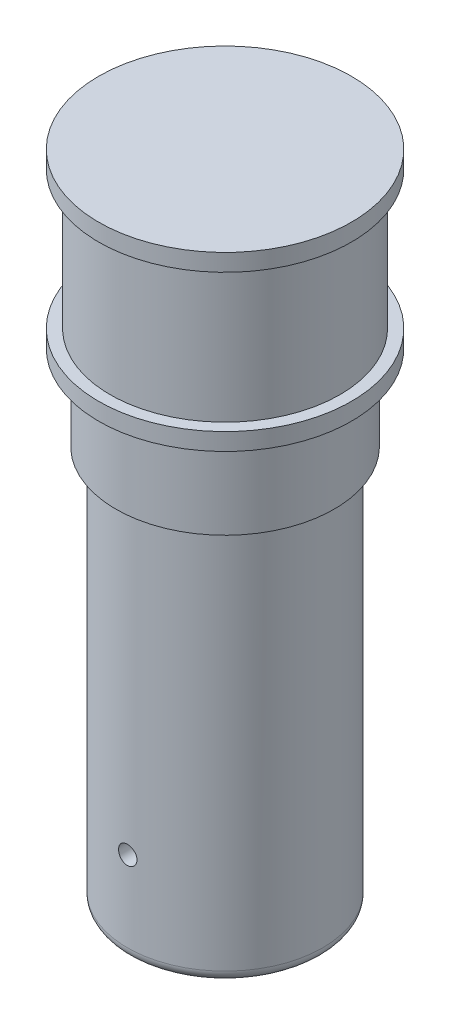
SolidWorks part; units mm, degrees
material "ABS"
ref_plane "Front Plane" through (0, 0, 0) normal (0, 0, 1) x (1, 0, 0)
ref_plane "Top Plane" through (0, 0, 0) normal (0, 1, 0) x (1, 0, 0)
ref_plane "Right Plane" through (0, 0, 0) normal (1, 0, 0) x (0, 0, -1)
sketch "Sketch1" plane through (0, 0, 0) normal (0, 0, 1) x (1, 0, 0)
  line L2 (-8.5, -41.925) -> (-8.5, -7.375)
  line L3 (-9.5, 0) -> (-11, 0)
  line L4 (-11, 0) -> (-11, 1.5)
  line L5 (-11, 1.5) -> (-10, 1.5)
  line L6 (-10, 1.5) -> (-10, 13.5)
  line L7 (-10, 13.5) -> (-11, 13.5)
  line L8 (-11, 13.5) -> (-11, 15)
  line L9 (-11, 15) -> (0, 15)
  line L10 (0, 15) -> (0, -27.925)
  line L11 (-4, -41.925) -> (-8.5, -41.925)
  line L12 (-4, -27.925) -> (-4, -41.925)
  line L13 (0, -27.925) -> (-4, -27.925)
  line L14 (-8.5, -7.375) -> (-9.5, -7.375)
  line L15 (-9.5, -7.375) -> (-9.5, 0)
  dimension "D1" = 8.5
  dimension "D2" = 1
  dimension "D3" = 41.925
  dimension "D4" = 1.5
  dimension "D5" = 4
  dimension "D6" = 14
  dimension "D7" = 15
  dimension "D8" = 10
  dimension "D9" = 34.55
  dimension "D10" = 1
revolve "Revolve1" add sketch "Sketch1" angle 360 about L10
fillet "Fillet1" radius 1 2 edges at (-8.5, -41.925, 0) (-4, -41.925, 0)
hole_wizard "M2x0.4 Tapped Hole1" positions "Sketch2" profile "Sketch3" tap size "M2x0.4" standard "ANSI Metric" end condition up to next
sketch "Sketch2" plane through (0, 0, 0) normal (0, 0, 1) x (1, 0, 0)
  line L0 (-7.5, -41.925) -> (7.5, -41.925) construction
  point P0 (0, -33.925)
  dimension "D1" = 8
sketch "Sketch3" plane through (0, -33.925, 0) normal (1, 0, 0) x (0, 1, 0)
  line L0 (0, 0) -> (0, 8.5)
  line L1 (0, 8.5) -> (0.8, 8.5)
  line L2 (0.8, 8.5) -> (0.8, 0)
  line L5 (0.8, 0) -> (0, 0)
  line L11 (0, -6.35) -> (0, 107.95) construction
  dimension "Thru Tap Drill Dia." = 1.6
  dimension "Thru Tap Drill Depth" = 8.5
cosmetic thread "Hole Thread1" parameters "D2"=2
